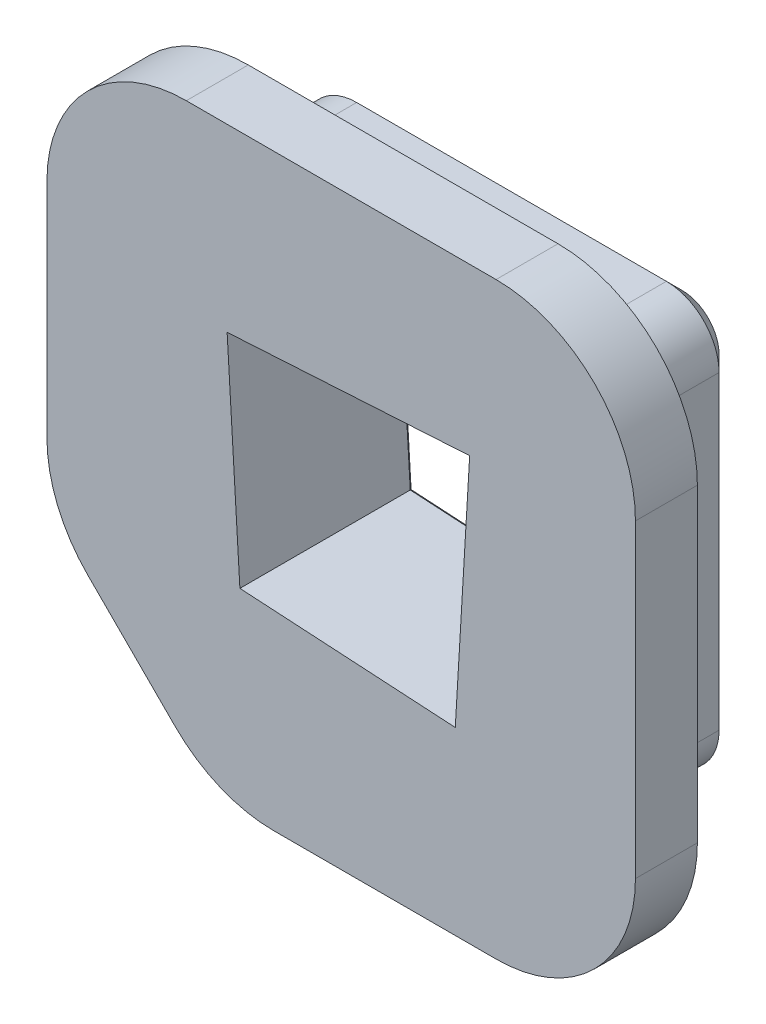
SolidWorks part; units mm, degrees
ref_plane "Front Plane" through (0, 0, 0) normal (0, 0, 1) x (1, 0, 0)
ref_plane "Top Plane" through (0, 0, 0) normal (0, 1, 0) x (1, 0, 0)
ref_plane "Right Plane" through (0, 0, 0) normal (1, 0, 0) x (0, 0, -1)
sketch "Sketch1" plane through (0, 0, 0) normal (0, 0, 1) x (1, 0, 0)
  line L51 (-12.9687, -11.2687) -> (-22.9687, -11.2687)
  line L52 (-11.2687, -22.9687) -> (-11.2687, -12.9687)
  line L53 (-20.1403, -24.6687) -> (-12.9687, -24.6687)
  line L54 (-24.1708, -21.3423) -> (-21.3423, -24.1708)
  line L55 (-24.6687, -12.9687) -> (-24.6687, -20.1403)
  line L56 (-12.9687, -11.2687) -> (-22.9687, -11.2687)
  line L57 (-11.2687, -22.9687) -> (-11.2687, -12.9687)
  line L58 (-20.1403, -24.6687) -> (-12.9687, -24.6687)
  line L59 (-24.1708, -21.3423) -> (-21.3423, -24.1708)
  line L60 (-24.6687, -12.9687) -> (-24.6687, -20.1403)
  arc A52 (-11.2687, -12.9687) -> (-12.9687, -11.2687) centre (-12.9687, -12.9687) ccw
  arc A53 (-12.9687, -24.6687) -> (-11.2687, -22.9687) centre (-12.9687, -22.9687) ccw
  arc A54 (-21.3423, -24.1708) -> (-20.1403, -24.6687) centre (-20.1403, -22.9687) ccw
  arc A55 (-24.6687, -20.1403) -> (-24.1708, -21.3423) centre (-22.9687, -20.1403) ccw
  arc A56 (-22.9687, -11.2687) -> (-24.6687, -12.9687) centre (-22.9687, -12.9687) ccw
  arc A57 (-11.2687, -12.9687) -> (-12.9687, -11.2687) centre (-12.9687, -12.9687) ccw
  arc A58 (-12.9687, -24.6687) -> (-11.2687, -22.9687) centre (-12.9687, -22.9687) ccw
  arc A59 (-21.3423, -24.1708) -> (-20.1403, -24.6687) centre (-20.1403, -22.9687) ccw
  arc A60 (-24.6687, -20.1403) -> (-24.1708, -21.3423) centre (-22.9687, -20.1403) ccw
  arc A61 (-22.9687, -11.2687) -> (-24.6687, -12.9687) centre (-22.9687, -12.9687) ccw
  dimension "D1" = 0.3
sketch "Sketch2" plane through (0, 0, 0) normal (0, 0, 1) x (1, 0, 0)
  line L67 (-26.1507, -23.3222) -> (-23.3222, -26.1507)
  line L68 (-20.1403, -27.4687) -> (-12.9687, -27.4687)
  line L69 (-8.4687, -22.9687) -> (-8.4687, -12.9687)
  line L70 (-12.9687, -8.4687) -> (-22.9687, -8.4687)
  line L71 (-27.4687, -12.9687) -> (-27.4687, -20.1403)
  line L72 (-26.1507, -23.3222) -> (-23.3222, -26.1507)
  line L73 (-20.1403, -27.4687) -> (-12.9687, -27.4687)
  line L74 (-8.4687, -22.9687) -> (-8.4687, -12.9687)
  line L75 (-12.9687, -8.4687) -> (-22.9687, -8.4687)
  line L76 (-27.4687, -12.9687) -> (-27.4687, -20.1403)
  arc A66 (-27.4687, -20.1403) -> (-26.1507, -23.3222) centre (-22.9687, -20.1403) ccw
  arc A67 (-23.3222, -26.1507) -> (-20.1403, -27.4687) centre (-20.1403, -22.9687) ccw
  arc A68 (-12.9687, -27.4687) -> (-8.4687, -22.9687) centre (-12.9687, -22.9687) ccw
  arc A69 (-8.4687, -12.9687) -> (-12.9687, -8.4687) centre (-12.9687, -12.9687) ccw
  arc A70 (-22.9687, -8.4687) -> (-27.4687, -12.9687) centre (-22.9687, -12.9687) ccw
  arc A71 (-27.4687, -20.1403) -> (-26.1507, -23.3222) centre (-22.9687, -20.1403) ccw
  arc A72 (-23.3222, -26.1507) -> (-20.1403, -27.4687) centre (-20.1403, -22.9687) ccw
  arc A73 (-12.9687, -27.4687) -> (-8.4687, -22.9687) centre (-12.9687, -22.9687) ccw
  arc A74 (-8.4687, -12.9687) -> (-12.9687, -8.4687) centre (-12.9687, -12.9687) ccw
  arc A75 (-22.9687, -8.4687) -> (-27.4687, -12.9687) centre (-22.9687, -12.9687) ccw
  dimension "D1" = 2.5
sketch "Sketch3" plane through (0, 0, 0) normal (0, 0, 1) x (1, 0, 0)
  line L0 (-21.6518, -14.2856) -> (-13.8206, -13.8206)
  line L1 (-17.75, -80) -> (-22.5, 0) construction
  line L2 (-17.75, -80) -> (-13, 0) construction
  line L3 (-13.8206, -13.8206) -> (-14.2856, -21.6518)
  line L4 (0, -22.5) -> (-80, -17.75) construction
  line L5 (-14.2856, -21.6518) -> (-21.2389, -21.2389)
  line L6 (-21.2389, -21.2389) -> (-21.6518, -14.2856)
  line L7 (-80, -17.75) -> (0, -13) construction
extrude "Boss-Extrude1" add sketch "Sketch2" along normal blind 2
extrude "Boss-Extrude2" add sketch "Sketch1" against normal blind 4
extrude "Cut-Extrude1" cut sketch "Sketch3" along normal through all both and the other way through all
chamfer "Chamfer1" distance 0.5 angle 45 14 edges at (-24.5393, -20.7908, -4) (-22.7566, -22.7566, -4) (-24.6687, -16.5545, -4) (-20.7908, -24.5393, -4) (-24.1708, -11.7666, -4) (-16.5545, -24.6687, -4) (-17.9687, -11.2687, -4) (-11.7666, -24.1708, -4) (-11.7666, -11.7666, -4) (-11.2687, -17.9687, -4) (-14.0531, -17.7362, -4) (-17.7362, -14.0531, -4) (-21.4454, -17.7623, -4) (-17.7623, -21.4454, -4)
